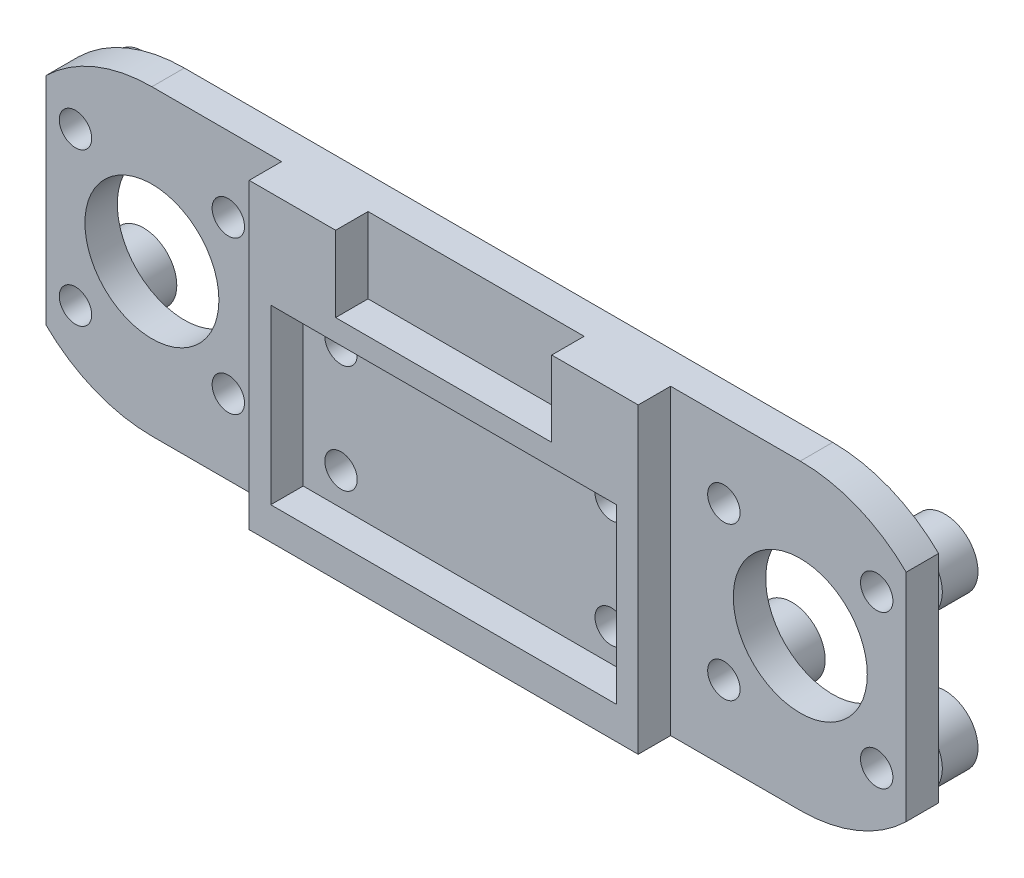
SolidWorks part; units mm, degrees
ref_plane "Front Plane" through (0, 0, 0) normal (0, 0, 1) x (1, 0, 0)
ref_plane "Top Plane" through (0, 0, 0) normal (0, 1, 0) x (1, 0, 0)
ref_plane "Right Plane" through (0, 0, 0) normal (1, 0, 0) x (0, 0, -1)
sketch "Sketch1" plane through (0, 0, 0) normal (0, 0, 1) x (1, 0, 0)
  line L0 (-39.8, 9.998) -> (-39.8, -9.998)
  line L1 (-30, -14) -> (30, -14)
  line L2 (-30, 14) -> (30, 14)
  line L6 (-30, 0) -> (30, 0) construction
  line L7 (39.8, 9.998) -> (39.8, -9.998)
  arc A0 (-30, 14) -> (-39.8, 9.998) centre (-30, 0) ccw
  arc A1 (-39.8, -9.998) -> (-30, -14) centre (-30, 0) ccw
  circle A2 centre (-30, 0) radius 6.2
  arc A7 (30, -14) -> (39.8, -9.998) centre (30, 0) ccw
  arc A8 (39.8, 9.998) -> (30, 14) centre (30, 0) ccw
  circle A9 centre (30, 0) radius 6.2
  point P3 (35.9012, 12.6955)
  point P7 (0, 0)
  point P8 (0, 0)
  point P9 (0, 0)
  point P10 (-36.0423, 12.629)
  point P18 (-30, 0)
  point P25 (30, 0)
  point P36 (30, 0)
  dimension "D2" = 9.8
  dimension "D3" = 12.4
  dimension "D4" = 14
  dimension "D1" = 28
  dimension "D7" = 60
extrude "Main" add sketch "Sketch1" along normal mid plane 3
sketch "Sketch2" plane through (0, 0, 1.5) normal (0, 0, -1) x (-1, 0, 0)
  line L0 (30, -14) -> (-30, -14) construction
  line L1 (39.8, 9.998) -> (39.8, -9.998) construction
  line L2 (18, 14) -> (10, 14)
  line L3 (18, 14) -> (18, -14)
  line L4 (18, -14) -> (-18, -14)
  line L5 (-18, 14) -> (-18, -14)
  line L6 (16, 5) -> (-16, 5)
  line L7 (16, 5) -> (16, -11)
  line L8 (16, -11) -> (-16, -11)
  line L9 (-16, 5) -> (-16, -11)
  line L10 (-39.8, -9.998) -> (-39.8, 9.998) construction
  line L11 (-30, 14) -> (30, 14) construction
  line L13 (-30, 14) -> (30, 14) construction
  line L14 (10, 14) -> (10, 7)
  line L15 (10, 7) -> (-10, 7)
  line L16 (-10, 7) -> (-10, 14)
  line L17 (-10, 14) -> (-18, 14)
  point P13 (0, -14)
  point P14 (0, 7)
  point P20 (0, 0)
  point P22 (0, 5)
  point P27 (16, -3)
  point P29 (0, -11)
  dimension "D1" = 16
  dimension "D2" = 36
  dimension "D4" = 7
  dimension "D5" = 32
  dimension "D6" = 79.6
  dimension "D9" = 3
  dimension "D10" = 2
  dimension "D11" = 20
  dimension "D12" = 3
extrude "Framework" add sketch "Sketch2" against normal blind 3
sketch "Sketch3" plane through (0, 0, -1.5) normal (0, 0, -1) x (-1, 0, 0)
  line L6 (16, 5) -> (16, -11) construction
  line L9 (16, -11) -> (-16, -11) construction
  circle A1 centre (12.5, -8) radius 1.5
  point P0 (16, -3)
  dimension "D1" = 3
  dimension "D2" = 5
  dimension "D3" = 12.5
  dimension "D4" = 8
  dimension "D5" = 3.5
  dimension "D6" = 3
extrude "FixHole" cut sketch "Sketch3" against normal through all
pattern_linear "HolePattern" count 2 spacing 25 along (1, 0, 0) count 2 spacing 10 along (0, 1, 0) of "FixHole"
sketch "Sketch4" plane through (0, 0, -1.5) normal (0, 0, 1) x (1, 0, 0)
  line L0 (-37.0711, 7.0711) -> (-22.9289, -7.0711) construction
  line L1 (-37.0711, -7.0711) -> (-22.9289, 7.0711) construction
  circle A0 centre (-37.0711, 7.0711) radius 3.075
  circle A1 centre (-22.9289, -7.0711) radius 3.075
  circle A2 centre (-22.9289, 7.0711) radius 3.075
  circle A3 centre (-37.0711, -7.0711) radius 3.075
  circle A4 centre (-37.0711, 7.0711) radius 1.5
  circle A5 centre (-22.9289, 7.0711) radius 1.5
  circle A6 centre (-30, 0) radius 6.2 construction
  circle A7 centre (-30, 0) radius 6.2 construction
  circle A8 centre (-37.0711, -7.0711) radius 1.5
  circle A9 centre (-22.9289, -7.0711) radius 1.5
  point P6 (-30, 0)
  point P10 (-30, 0)
  dimension "D1" = 6.15
  dimension "D3" = 3
  dimension "D2" = 20
extrude "ForLMK6UU" add sketch "Sketch4" against normal blind 3.3
sketch "Sketch5" plane through (0, 0, 1.5) normal (0, 0, 1) x (1, 0, 0)
  circle A0 centre (-37.0711, 7.0711) radius 1.5
  circle A1 centre (-37.0711, 7.0711) radius 1.5 construction
  circle A2 centre (-22.9289, 7.0711) radius 1.5
  circle A3 centre (-22.9289, 7.0711) radius 1.5 construction
  circle A4 centre (-37.0711, -7.0711) radius 1.5
  circle A5 centre (-37.0711, -7.0711) radius 1.5 construction
  circle A6 centre (-22.9289, -7.0711) radius 1.5
  circle A7 centre (-22.9289, -7.0711) radius 1.5 construction
extrude "Cut-Extrude1" cut sketch "Sketch5" against normal through all
mirror "Mirror1" about plane through (0, 0, 0) normal (1, 0, 0) of "Cut-Extrude1", "ForLMK6UU"
